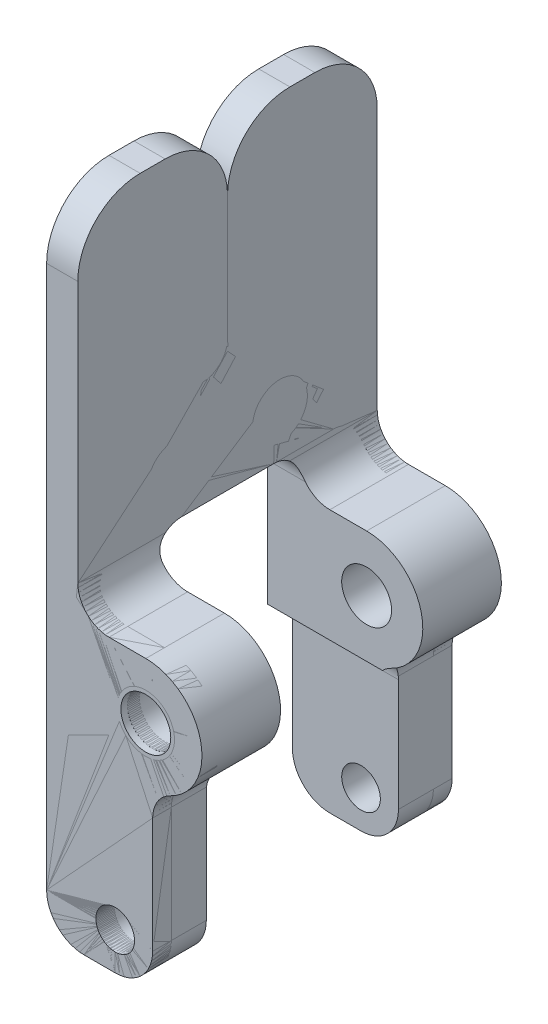
SolidWorks part; units mm, degrees
material "aluminio"
ref_plane "Alzado" through (0, 0, 0) normal (0, 0, 1) x (1, 0, 0)
ref_plane "Planta" through (0, 0, 0) normal (0, 1, 0) x (1, 0, 0)
ref_plane "Vista lateral" through (0, 0, 0) normal (1, 0, 0) x (0, 0, -1)
sketch "Croquis1" plane through (0, 0, 0) normal (0, 0, 1) x (1, 0, 0)
  line L0 (-5.5, 0) -> (-5.5, 31.5)
  line L1 (-5.5, 31.5) -> (-3, 31.5)
  line L2 (-3, 31.5) -> (-3, 20.05)
  line L3 (-3, 20.05) -> (2.45, 20.05)
  line L4 (0, -3) -> (-2.5, -3)
  line L5 (3, 0) -> (3, 11.0837)
  arc A0 (-5.5, 0) -> (-2.5, -3) centre (-2.5, 0) ccw
  arc A1 (3, 11.0837) -> (2.45, 20.05) centre (2.45, 15.55) ccw
  circle A2 centre (2.45, 15.55) radius 2
  circle A3 centre (0, 0) radius 1.55
  arc A5 (0, -3) -> (3, 0) centre (0, 0) ccw
  dimension "D1" = 5.5
  dimension "D2" = 31.5
  dimension "D4" = 9
  dimension "D7" = 4
  dimension "D8" = 3.1
  dimension "D9" = 3
  dimension "D12" = 3
  dimension "D3" = 2.5
  dimension "D5" = 15.55
  dimension "D6" = 2.45
extrude "Saliente-Extruir1" add sketch "Croquis1" along normal blind 24
sketch "Croquis2" plane through (-5.5, 0, 0) normal (-1, 0, 0) x (0, 0, 1)
  line L0 (24, -3) -> (0, -3) construction
  line L1 (1.5, -3) -> (19.7, -3)
  line L2 (1.5, -3) -> (1.5, 23)
  line L3 (1.5, 23) -> (17.7, 23)
  line L4 (17.7, 23) -> (17.7, 11)
  line L5 (1.5, 23) -> (0, 23) construction
  line L6 (0, 31.5) -> (0, 0) construction
  line L7 (0, 0) -> (0, -3) construction
  line L10 (17.7, 11) -> (19.7, 11)
  line L11 (19.7, 11) -> (19.7, -3)
  dimension "D1" = 16.2
  dimension "D2" = 26
  dimension "D3" = 1.5
  dimension "D4" = 12
  dimension "D5" = 2
extrude "Cortar-Extruir1" cut sketch "Croquis2" against normal blind 20
fillet "Redondeo1" radius 8 2 edges at (-4.25, 31.5, 0) (-4.25, 31.5, 24)
fillet "Redondeo2" radius 2 3 edges at (-1.25, 11, 19.7) (-4.25, 23, 17.7) (-4.25, 23, 1.5)
fillet "Redondeo5" radius 2.5 4 edges at (3, 11.0837, 0.75) (-3, 20.05, 20.85) (3, 11.0837, 20.85) (-3, 20.05, 0.75)
sketch "Croquis3" plane through (-5.5, 0, 0) normal (-1, 0, 0) x (0, 0, 1)
  line L0 (16, 31.5) -> (8, 31.5) construction
  line L1 (0, 23.5) -> (0, 0) construction
  circle A0 centre (7.8, 26.4) radius 2.2
  dimension "D1" = 4.4
  dimension "D2" = 5.1
  dimension "D3" = 7.8
extrude "Cortar-Extruir2" cut sketch "Croquis3" against normal blind 20
sketch "Croquis4" plane through (0, 23, 0) normal (0, -1, 0) x (1, 0, 0)
  line L0 (-5.5, 15.7) -> (-5.5, 3.5) construction
  line L1 (-5.5, 11.4) -> (-4, 11.4)
  line L2 (-5.5, 11.4) -> (-5.5, 4.2)
  line L3 (-5.5, 4.2) -> (-4, 4.2)
  line L4 (-4, 11.4) -> (-4, 4.2)
  line L5 (-5.5, 10) -> (-5.5, 5.6) construction
  point P8 (-5.5, 7.8)
  dimension "D1" = 7.2
  dimension "D2" = 1.5
extrude "Cortar-Extruir3" cut sketch "Croquis4" against normal blind 20
sketch "Croquis5" plane through (-5.5, 0, 0) normal (-1, 0, 0) x (0, 0, 1)
  line L0 (0, 23.5) -> (0, 48.5)
  line L1 (0, 48.5) -> (12, 48.5)
  line L2 (12, 30) -> (4.2, 30)
  line L5 (12, 30) -> (12, 48.5)
  line L6 (4.2, 30.5399) -> (4.2, 23) construction
  line L7 (4.2, 30) -> (0, 23.5)
  line L8 (8, 31.5) -> (11.4, 31.5) construction
  line L9 (16, 31.5) -> (11.4, 31.5) construction
  dimension "D1" = 4
  dimension "D2" = 1.5
  dimension "D3" = 17
extrude "Saliente-Extruir2" add sketch "Croquis5" against normal up to surface (2.5 mm away) up to face at (-3, 24.2, 7.8)
fillet "Redondeo7" radius 2 1 edges at (-4.25, 31.5, 12)
sketch "Croquis6" plane through (-5.5, 0, 0) normal (-1, 0, 0) x (0, 0, 1)
  line L0 (11.4, 30) -> (11.4, 23) construction
  line L1 (11.4, 28.5) -> (4.2, 28.5)
  line L2 (11.4, 28.5) -> (11.4, 31.5)
  line L3 (11.4, 31.5) -> (4.2, 31.5)
  line L4 (4.2, 28.5) -> (4.2, 31.5)
  line L5 (4.2, 30) -> (4.2, 23) construction
  line L6 (4.2, 23) -> (11.4, 23) construction
  dimension "D1" = 5.5
  dimension "D2" = 3
extrude "Cortar-Extruir4" cut sketch "Croquis6" against normal up to surface (1.5 mm away) up to face at (-4, 26.4, 5.6)
fillet "Redondeo8" radius 3 2 edges at (-4.75, 31.5, 11.4) (-4.75, 31.5, 4.2)
fillet "Redondeo9" radius 5 2 edges at (-4.25, 48.5, 0) (-4.25, 48.5, 12)
chamfer "Chaflán1" distance 0.3 angle 60 1 edges at (4.45, 15.55, 24) first distance on face at (4.45, 15.55, 24)
ref_plane "Plano1" through (0, 0, 12) normal (0, 0, 1) x (1, 0, 0)
mirror "Simetría1" about plane through (0, 0, 12) normal (0, 0, 1) of bodies 123
